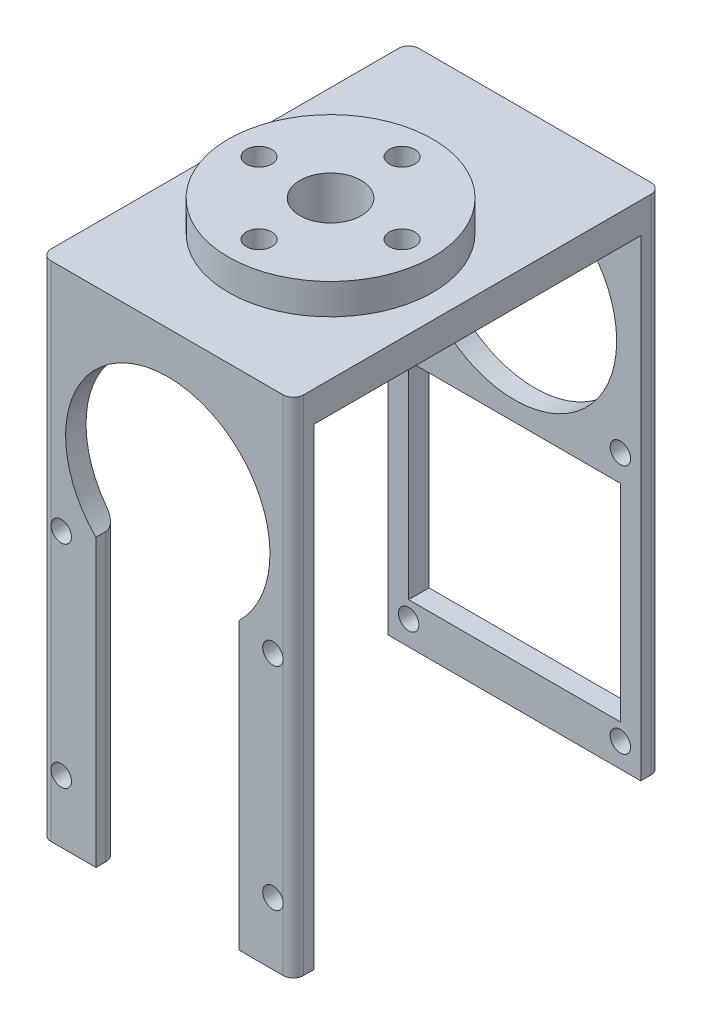
SolidWorks part; units mm, degrees
ref_plane "前视基准面" through (0, 0, 0) normal (0, 0, 1) x (1, 0, 0)
ref_plane "上视基准面" through (0, 0, 0) normal (0, 1, 0) x (1, 0, 0)
ref_plane "右视基准面" through (0, 0, 0) normal (1, 0, 0) x (0, 0, -1)
sketch "草图1" plane through (0, 0, 0) normal (0, 0, 1) x (1, 0, 0)
  line L1 (0, 0) -> (24.72, 0)
  line L2 (0, 0) -> (0, 49.22)
  line L3 (0, 49.22) -> (24.72, 49.22)
  line L4 (24.72, 0) -> (24.72, 49.22)
  dimension "D1" = 24.72
  dimension "D2" = 49.22
extrude "凸台-拉伸1" add sketch "草图1" along normal blind 36
sketch "草图3" plane through (0, 0, 0) normal (0, -1, 0) x (1, 0, 0)
  line L0 (0, 0) -> (24.72, 0) construction
  line L1 (0, 34) -> (24.72, 34)
  line L2 (0, 34) -> (0, 2)
  line L3 (0, 2) -> (24.72, 2)
  line L4 (24.72, 34) -> (24.72, 2)
  line L5 (24.72, 36) -> (24.72, 0) construction
  line L7 (0, 36) -> (24.72, 36) construction
  dimension "D1" = 2
  dimension "D2" = 2
  dimension "D3" = 24.72
  dimension "D4" = 0
extrude "切除-拉伸1" cut sketch "草图3" against normal blind 46.22
sketch "草图4" plane through (0, 0, 2) normal (0, 0, 1) x (1, 0, 0)
  line L0 (24.72, 0) -> (24.72, 49.22) construction
  line L1 (0, 49.22) -> (0, 0) construction
  line L2 (0, 0) -> (24.72, 0) construction
  line L3 (24.72, 49.22) -> (0, 49.22) construction
  line L5 (2, 24.22) -> (22.72, 24.22)
  line L6 (2, 24.22) -> (2, 4)
  line L7 (2, 4) -> (22.72, 4)
  line L8 (22.72, 24.22) -> (22.72, 4)
  circle A0 centre (2, 2.36) radius 1
  circle A1 centre (22.72, 2.36) radius 1
  circle A2 centre (22.72, 26.81) radius 1
  circle A3 centre (2, 26.81) radius 1
  circle A4 centre (12.36, 36.11) radius 10
  dimension "D1" = 2
  dimension "D2" = 2
  dimension "D3" = 2
  dimension "D4" = 2
  dimension "D5" = 20
  dimension "D6" = 2
  dimension "D7" = 2
  dimension "D8" = 2
  dimension "D9" = 2
  dimension "D10" = 2.36
  dimension "D11" = 2.36
  dimension "D12" = 24.45
  dimension "D13" = 24.45
  dimension "D14" = 12.36
  dimension "D15" = 13.11
  dimension "D16" = 2
  dimension "D17" = 2
  dimension "D18" = 4
  dimension "D19" = 25
extrude "切除-拉伸2" cut sketch "草图4" against normal blind 2
sketch "草图6" plane through (0, 0, 36) normal (0, 0, 1) x (1, 0, 0)
  line L0 (0, 0) -> (24.72, 0) construction
  line L1 (5.4, 28) -> (19.4, 28)
  line L2 (5.4, 28) -> (5.4, 0)
  line L3 (5.4, 0) -> (19.4, 0)
  line L4 (19.4, 28) -> (19.4, 0)
  line L5 (0, 49.22) -> (0, 0) construction
  line L6 (24.72, 0) -> (24.72, 49.22) construction
  circle A0 centre (2, 6.11) radius 1
  circle A1 centre (22.72, 6.11) radius 1
  circle A2 centre (22.72, 26.81) radius 1
  circle A3 centre (2, 26.81) radius 1
  circle A4 centre (12.4284, 35.11) radius 10
  line M7 (0, 0) -> (24.72, 0)
  dimension "D1" = 2
  dimension "D2" = 2
  dimension "D3" = 2
  dimension "D4" = 2
  dimension "D5" = 20
  dimension "D6" = 2
  dimension "D7" = 6.11
  dimension "D8" = 6.11
  dimension "D9" = 2
  dimension "D10" = 2
  dimension "D11" = 20.7
  dimension "D12" = 20.7
  dimension "D13" = 2
  dimension "D14" = 35.11
  dimension "D15" = 14
  dimension "D16" = 5.32
  dimension "D17" = 28
extrude "切除-拉伸3" cut sketch "草图6" against normal blind 6 contours L4 A4 L2 L1 | A4 L2 L4 M7 | A3 | A1 | L2 A4 L4 L1 | A0 | A2 region at (12.4285, 35.92, 36) region at (12.428, 26.8283, 36) region at (12.3978, 13.0136, 36) region at (22.72, 6.11, 36) region at (2, 26.81, 36)
sketch "草图7" plane through (0, 49.22, 0) normal (0, 1, 0) x (1, 0, 0)
  line L0 (24.72, 0) -> (0, 0) construction
  line L1 (24.72, -36) -> (0, -36) construction
  line L2 (24.72, -36) -> (24.72, 0) construction
  circle A0 centre (12.36, -20) radius 10
  dimension "D1" = 20
  dimension "D2" = 20
  dimension "D3" = 36
  dimension "D4" = 12.36
extrude "凸台-拉伸2" add sketch "草图7" along normal blind 3
sketch "草图8" plane through (0, 52.22, 0) normal (0, 1, 0) x (1, 0, 0)
  line L0 (0, -36) -> (0, 0) construction
  line L2 (24.72, 0) -> (0, 0) construction
  line L4 (24.72, -36) -> (24.72, 0) construction
  circle A0 centre (12.36, -13) radius 1.25
  circle A1 centre (12.36, -27) radius 1.25
  circle A2 centre (19.36, -20) radius 1.25
  circle A3 centre (5.36, -20) radius 1.25
  dimension "D1" = 2.5
  dimension "D2" = 2.5
  dimension "D3" = 2.5
  dimension "D4" = 2.5
  dimension "D5" = 12.36
  dimension "D6" = 12.36
  dimension "D9" = 14
  dimension "D10" = 14
  dimension "D11" = 13
  dimension "D12" = 5.36
  dimension "D7" = 20
  dimension "D8" = 20
extrude "切除-拉伸4" cut sketch "草图8" against normal blind 8
fillet "圆角1" radius 2 1 edges at (12.36, 46.22, 11.75)
fillet "圆角2" radius 2 1 edges at (19.36, 46.22, 18.75)
fillet "圆角3" radius 2 1 edges at (12.36, 46.22, 25.75) conic rho 0.5
fillet "圆角4" radius 2 1 edges at (5.36, 46.22, 18.75)
fillet "圆角5" radius 1 1 edges at (0, 24.61, 36)
fillet "圆角6" radius 1 1 edges at (24.72, 24.61, 36)
fillet "圆角7" radius 1 1 edges at (0, 24.61, 0)
fillet "圆角8" radius 1 1 edges at (24.72, 24.61, 0)
fillet "圆角9" radius 1 1 edges at (19.4, 13.9704, 34)
fillet "圆角10" radius 1 1 edges at (5.4, 13.9983, 34)
sketch "草图9" plane through (0, 52.22, 0) normal (0, 1, 0) x (1, 0, 0)
  circle A0 centre (12.36, -20) radius 3
  circle A1 centre (12.36, -20) radius 10 construction
  dimension "D1" = 0
  dimension "D2" = 6
extrude "切除-拉伸5" cut sketch "草图9" against normal blind 10
